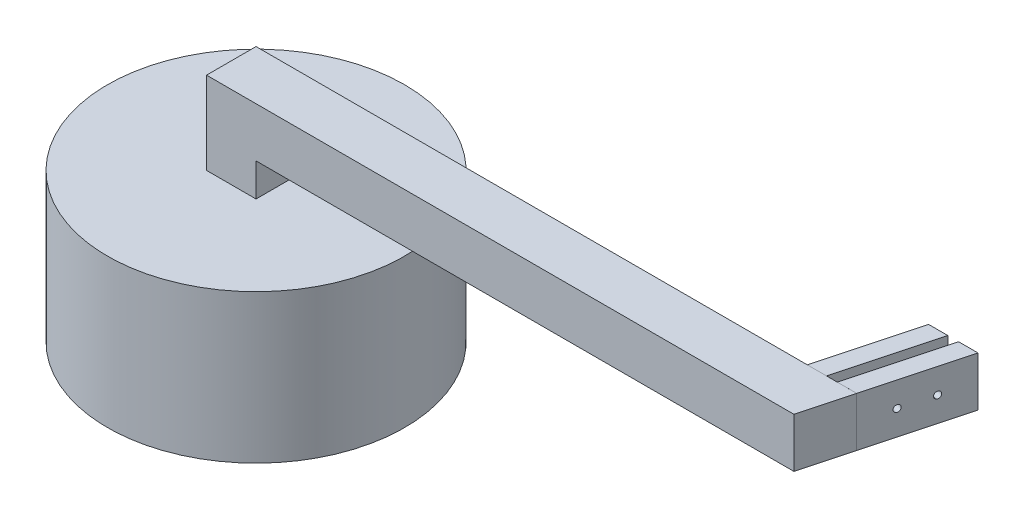
SolidWorks part; units mm, degrees
ref_plane "Front Plane" through (0, 0, 0) normal (0, 0, 1) x (1, 0, 0)
ref_plane "Top Plane" through (0, 0, 0) normal (0, 1, 0) x (1, 0, 0)
ref_plane "Right Plane" through (0, 0, 0) normal (1, 0, 0) x (0, 0, -1)
sketch "Sketch1" plane through (0, 0, 0) normal (0, 1, 0) x (1, 0, 0)
  circle A0 centre (0, 0) radius 90
  dimension "D1" = 180
extrude "Boss-Extrude1" add sketch "Sketch1" along normal blind 90
sketch "Sketch2" plane through (0, 90, 0) normal (0, 1, 0) x (1, 0, 0)
  line L0 (0, 90) -> (0, -90) construction
  line L2 (-15, 15) -> (15, 15)
  line L3 (-15, 15) -> (-15, -15)
  line L4 (-15, -15) -> (15, -15)
  line L5 (15, 15) -> (15, -15)
  line L6 (-15, 15) -> (15, -15) construction
  line L7 (-15, -15) -> (15, 15) construction
  circle A0 centre (0, 0) radius 90 construction
  point P5 (0, 0)
  dimension "D1" = 30
  dimension "D2" = 30
extrude "Boss-Extrude2" add sketch "Sketch2" along normal blind 50
sketch "Sketch3" plane through (15, 0, 0) normal (1, 0, 0) x (0, 0, -1)
  line L0 (15, 140) -> (15, 90) construction
  line L1 (-15, 140) -> (15, 140)
  line L2 (-15, 140) -> (-15, 110)
  line L3 (-15, 110) -> (15, 110)
  line L4 (15, 140) -> (15, 110)
  dimension "D1" = 30
extrude "Boss-Extrude3" add sketch "Sketch3" along normal blind 120
sketch "Sketch4" plane through (0, 140, 0) normal (0, 1, 0) x (1, 0, 0)
  line L0 (0, 0) -> (450, 450) construction
  line L1 (0, 0) -> (736.1585, 0) construction
  line L2 (450, 450) -> (249.4695, -298.3902) construction
  line L3 (348.9703, 14.9963) -> (340.9328, -15)
  line L4 (135, -15) -> (340.9328, -15)
  line L5 (135, -15) -> (135, 14.9963)
  line L6 (135, 14.9963) -> (348.9703, 14.9963)
  line L7 (886, 14.9963) -> (16, 14.9963) construction
  line L8 (135, 15) -> (135, -15) construction
  circle A0 centre (450, 450) radius 1.5 construction
  point P4 (329.4229, 0)
  dimension "D1" = 30
  dimension "D2" = 15
extrude "Boss-Extrude4" add sketch "Sketch4" against normal up to vertex (30 mm away) up to point (135, 110, -15)
sketch "Sketch5" plane through (0, 0, -15) normal (0, 0, -1) x (-1, 0, 0)
  line L0 (-135, 110) -> (-15, 110) construction
  line L1 (-348.9703, 140) -> (-318.9703, 140)
  line L2 (-348.9703, 140) -> (-348.9703, 110)
  line L3 (-348.9703, 110) -> (-318.9703, 110)
  line L4 (-318.9703, 140) -> (-318.9703, 110)
  line L5 (-348.9703, 110) -> (-348.9703, 140) construction
  line L6 (-348.9703, 140) -> (-135, 140) construction
  dimension "D1" = 30
extrude "Boss-Extrude5" add sketch "Sketch5" along direction (0.2588, 0, -0.9659) on the side of the normal blind 60
sketch "Sketch6" plane through (0, 140, 0) normal (0, 1, 0) x (1, 0, 0)
  line L0 (349.4994, 72.9555) -> (325.9318, -15) construction
  line L1 (334.4994, 72.9555) -> (364.4994, 72.9555) construction
  line L2 (-15, -15) -> (340.9328, -15) construction
  line L3 (340.9328, -15) -> (348.9703, 14.9963) construction
  line L4 (337.2573, 15) -> (352.7864, 72.9555)
  line L5 (337.2573, 15) -> (330.6832, 15)
  line L6 (352.7864, 72.9555) -> (346.2124, 72.9555)
  line L7 (330.6832, 15) -> (346.2124, 72.9555)
  line L15 (318.9703, 15) -> (348.9703, 15) construction
  dimension "D1" = 6.35
  dimension "D2" = 3.175
  dimension "D3" = 0
extrude "Cut-Extrude1" cut sketch "Sketch6" against normal up to vertex (30 mm away) up to point (334.4994, 110, -72.9555)
hole_wizard "#10-32 Tapped Hole1" positions "Sketch9" profile "Sketch8" tap size "#10-32" standard "ANSI Inch" end condition through all
sketch "Sketch9" plane through (321.8437, 0, 86.2378) normal (0.9659, 0, 0.2588) x (0.2588, 0, -0.9659)
  line L0 (164.809, 125) -> (73.6411, 125) construction
  line L1 (164.809, 140) -> (164.809, 110) construction
  point P0 (144.809, 125)
  point P2 (124.809, 125)
  dimension "D1" = 20
  dimension "D2" = 20
sketch "Sketch8" plane through (359.323, 125, -53.637) normal (0, 1, 0) x (0.2588, 0, -0.9659)
  line L0 (0, 0) -> (0, 443.4241)
  line L1 (0, 443.4241) -> (2.0193, 443.4241)
  line L2 (2.0193, 443.4241) -> (2.0193, 0)
  line L5 (2.0193, 0) -> (0, 0)
  line L11 (0, -6.35) -> (0, 107.95) construction
  dimension "Thru Tap Drill Dia." = 4.0386
  dimension "Thru Tap Drill Depth" = 443.4241
cosmetic thread "Hole Thread1" parameters "D2"=4.826
cosmetic thread "Hole Thread2" parameters "D2"=4.826
